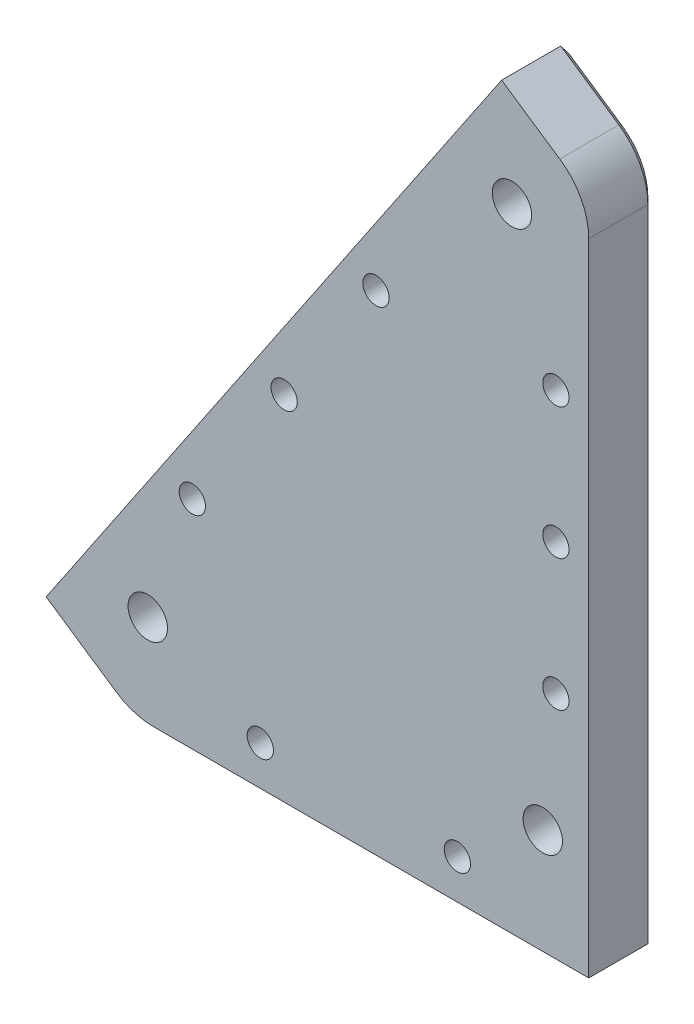
SolidWorks part; units mm, degrees
ref_plane "Спереди" through (0, 0, 0) normal (0, 0, 1) x (1, 0, 0)
ref_plane "Сверху" through (0, 0, 0) normal (0, 1, 0) x (1, 0, 0)
ref_plane "Справа" through (0, 0, 0) normal (1, 0, 0) x (0, 0, -1)
other "Configuration Table"
sketch "Эскиз1" plane through (0, 0, 0) normal (0, 0, 1) x (1, 0, 0)
  line L0 (-5.0675, -2.1479) -> (-19.0473, -22.8739) construction
  line L1 (-8.6977, -49.8739) -> (21.3023, -49.8739) construction
  line L2 (36.3023, 19.1261) -> (36.3023, -0.8739) construction
  line L3 (36.3023, -0.8739) -> (36.3023, -20.8739) construction
  line L4 (-5.0675, -2.1479) -> (8.9124, 18.578) construction
  line L5 (41.3023, -55.8739) -> (41.3023, 41.6097)
  line L6 (36.8942, 49.9001) -> (28.0377, 55.8739)
  line L7 (28.0377, 55.8739) -> (-41.3023, -46.9268)
  line L8 (-41.3023, -46.9268) -> (-30.5723, -54.1642)
  line L9 (-24.9804, -55.8739) -> (41.3023, -55.8739)
  circle A0 centre (34.3023, -39.8739) radius 3
  circle A1 centre (29.6177, 40.3335) radius 3
  circle A2 centre (-25.8318, -41.8739) radius 3
  circle A3 centre (-19.0473, -22.8739) radius 2
  circle A4 centre (-5.0675, -2.1479) radius 2
  circle A5 centre (8.9124, 18.578) radius 2
  circle A6 centre (-8.6977, -49.8739) radius 2
  circle A7 centre (21.3023, -49.8739) radius 2
  circle A8 centre (36.3023, 19.1261) radius 2
  circle A9 centre (36.3023, -0.8739) radius 2
  circle A10 centre (36.3023, -20.8739) radius 2
  arc A11 (41.3023, 41.6097) -> (36.8942, 49.9001) centre (31.3023, 41.6097) ccw
  arc A12 (-30.5723, -54.1642) -> (-24.9804, -55.8739) centre (-24.9804, -45.8739) ccw
  dimension "D1" = 6
  dimension "D3" = 4
  dimension "D2" = 50
  dimension "D4" = 30
  dimension "D5" = 40
extrude "Бобышка-Вытянуть1" add sketch "Эскиз1" along normal blind 10
sketch "Эскиз2" plane through (0, 0, 0) normal (0, 0, -1) x (-1, 0, 0)
  circle A0 centre (-36.3023, 19.1261) radius 4
  circle A1 centre (-36.3023, -0.8739) radius 4
  circle A2 centre (-36.3023, -20.8739) radius 4
  circle A3 centre (-21.3023, -49.8739) radius 4
  circle A4 centre (8.6977, -49.8739) radius 4
  circle A5 centre (19.0473, -22.8739) radius 4
  circle A6 centre (5.0675, -2.1479) radius 4
  circle A7 centre (-8.9124, 18.578) radius 4
  dimension "D1" = 8
extrude "Вырез-Вытянуть1" cut sketch "Эскиз2" against normal blind 1.5
chamfer "Фаска1" distance 1 angle 45 7 edges at (-35.9373, -50.5455, 0) (-27.9041, -55.4369, 0) (8.161, -55.8739, 0) (-6.6323, 4.4735, 0) (41.3023, -7.1321, 0) (32.4659, 52.887, 0) (40.1317, 46.3044, 0)
